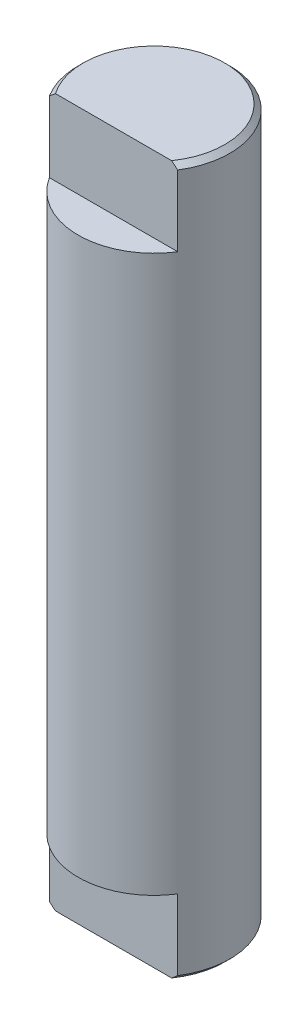
SolidWorks part; units mm, degrees
ref_plane "Plan de face" through (0, 0, 0) normal (0, 0, 1) x (1, 0, 0)
ref_plane "Plan de dessus" through (0, 0, 0) normal (0, 1, 0) x (1, 0, 0)
ref_plane "Plan de droite" through (0, 0, 0) normal (1, 0, 0) x (0, 0, -1)
ref_plane "Plan1" through (0, 0, 10.4) normal (0, 0, -1) x (-1, 0, 0)
sketch "Esquisse1" plane through (0, 0, 10.4) normal (0, 0, -1) x (-1, 0, 0)
  line L0 (-2.3578, -12.6371) -> (-0.8578, -12.6371)
  line L1 (-0.8578, -12.6371) -> (-0.8578, 1.3629)
  line L2 (-0.8578, 1.3629) -> (-2.3578, 1.3629)
  line L3 (-2.3578, 1.3629) -> (-2.3578, -12.6371)
  line L4 (-0.8578, -12.6371) -> (-0.8578, 1.3629) construction
  dimension "D1" = 14
  dimension "D2" = 1.5
revolve "Révolution1" add sketch "Esquisse1" angle 360 about L4 reverse direction yes
sketch "Esquisse2" plane through (0, 1.3629, 0) normal (0, 1, 0) x (-1, 0, 0)
  line L0 (-2.1267, 11.2) -> (0.4111, 11.2)
  arc A0 (0.4111, 11.2) -> (-2.1267, 11.2) centre (-0.8578, 10.4) ccw
extrude "Enlèv. mat.-Extru.1" cut sketch "Esquisse2" against normal blind 1.5
sketch "Esquisse3" plane through (0, -12.6371, 0) normal (0, -1, 0) x (1, 0, 0)
  line L0 (-0.4111, 11.2) -> (2.1267, 11.2)
  arc A0 (2.1267, 11.2) -> (-0.4111, 11.2) centre (0.8578, 10.4) ccw
extrude "Enlèv. mat.-Extru.2" cut sketch "Esquisse3" against normal blind 1.5
chamfer "Chanfrein1" distance 0.1 angle 45 1 edges at (0.8578, 1.3629, 8.9)
chamfer "Chanfrein2" distance 0.1 angle 45 1 edges at (0.8578, -12.6371, 8.9)
